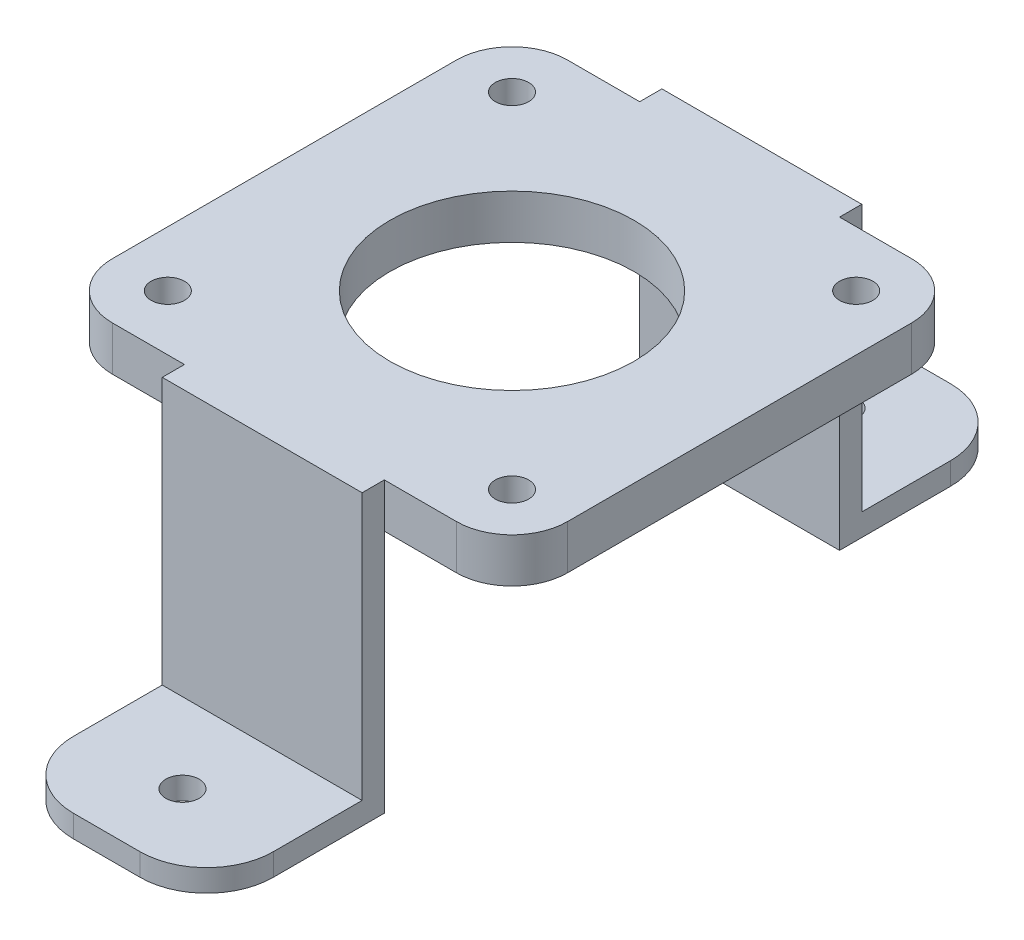
SolidWorks part; units mm, degrees
ref_plane "Спереди" through (0, 0, 0) normal (0, 0, 1) x (1, 0, 0)
ref_plane "Сверху" through (0, 0, 0) normal (0, 1, 0) x (1, 0, 0)
ref_plane "Справа" through (0, 0, 0) normal (1, 0, 0) x (0, 0, -1)
other "Configuration Table"
sketch "Эскиз2" plane through (0, 0, 0) normal (0, 1, 0) x (1, 0, 0)
  line L0 (0, 0) -> (-63.8997, 0) construction
  line L1 (-15.5, -20.5) -> (15.5, -20.5)
  line L2 (-20.5, -15.5) -> (-20.5, 15.5)
  line L3 (-15.5, 20.5) -> (15.5, 20.5)
  line L4 (20.5, -15.5) -> (20.5, 15.5)
  line L5 (-20.5, -20.5) -> (20.5, 20.5) construction
  line L6 (-20.5, 20.5) -> (20.5, -20.5) construction
  circle A0 centre (0, 0) radius 11
  circle A1 centre (-15.5, 15.5) radius 1.5
  circle A2 centre (15.5, -15.5) radius 1.5
  circle A3 centre (-15.5, -15.5) radius 1.5
  circle A4 centre (15.5, 15.5) radius 1.5
  arc A5 (-15.5, 20.5) -> (-20.5, 15.5) centre (-15.5, 15.5) ccw
  arc A6 (20.5, 15.5) -> (15.5, 20.5) centre (15.5, 15.5) ccw
  arc A7 (-15.5, -20.5) -> (-20.5, -15.5) centre (-15.5, -15.5) cw
  arc A8 (15.5, -20.5) -> (20.5, -15.5) centre (15.5, -15.5) ccw
  point P0 (0, 0)
  dimension "D3" = 22
  dimension "D4" = 3
  dimension "D7" = 5
  dimension "D8" = 5
  dimension "D9" = 5
  dimension "D10" = 5
  dimension "D1" = 41
  dimension "D2" = 41
  dimension "D5" = 31
  dimension "D6" = 31
extrude "Бобышка-Вытянуть1" add sketch "Эскиз2" along normal blind 4
sketch "Эскиз3" plane through (0, 0, 20.5) normal (0, 0, 1) x (1, 0, 0)
  line L0 (-15.5, 4) -> (15.5, 4) construction
  line L1 (-9, 4) -> (9, 4)
  line L2 (-9, 4) -> (-9, -22)
  line L3 (-9, -22) -> (9, -22)
  line L4 (9, 4) -> (9, -22)
  line L5 (-20.5, 4) -> (-20.5, 0) construction
  point P8 (0, 0)
  dimension "D1" = 18
  dimension "D2" = 11.5
  dimension "D3" = 26
extrude "Бобышка-Вытянуть2" add sketch "Эскиз3" along normal blind 2 contours L1 L4 L3 L2
sketch "Эскиз4" plane through (0, -22, 0) normal (0, -1, 0) x (1, 0, 0)
  line L1 (9, 22.5) -> (-9, 22.5)
  line L2 (9, 22.5) -> (9, 30.5)
  line L3 (3, 36.5) -> (-3, 36.5)
  line L4 (-9, 22.5) -> (-9, 30.5)
  arc A0 (-3, 36.5) -> (-9, 30.5) centre (-3, 30.5) ccw
  arc A1 (3, 36.5) -> (9, 30.5) centre (3, 30.5) cw
  point P7 (-9, 36.5)
  dimension "D2" = 6
  dimension "D3" = 6
  dimension "D1" = 14
extrude "Бобышка-Вытянуть3" add sketch "Эскиз4" against normal blind 2
sketch "Эскиз5" plane through (0, -20, 0) normal (0, 1, 0) x (1, 0, 0)
  circle A0 centre (0, -29.6787) radius 1.5
  dimension "D1" = 3
extrude "Вырез-Вытянуть1" cut sketch "Эскиз5" against normal through all contours A0
mirror "Зеркальное отражение1" about plane through (0, 0, 0) normal (0, 0, 1) of "Вырез-Вытянуть1", "Бобышка-Вытянуть3", "Бобышка-Вытянуть2"
